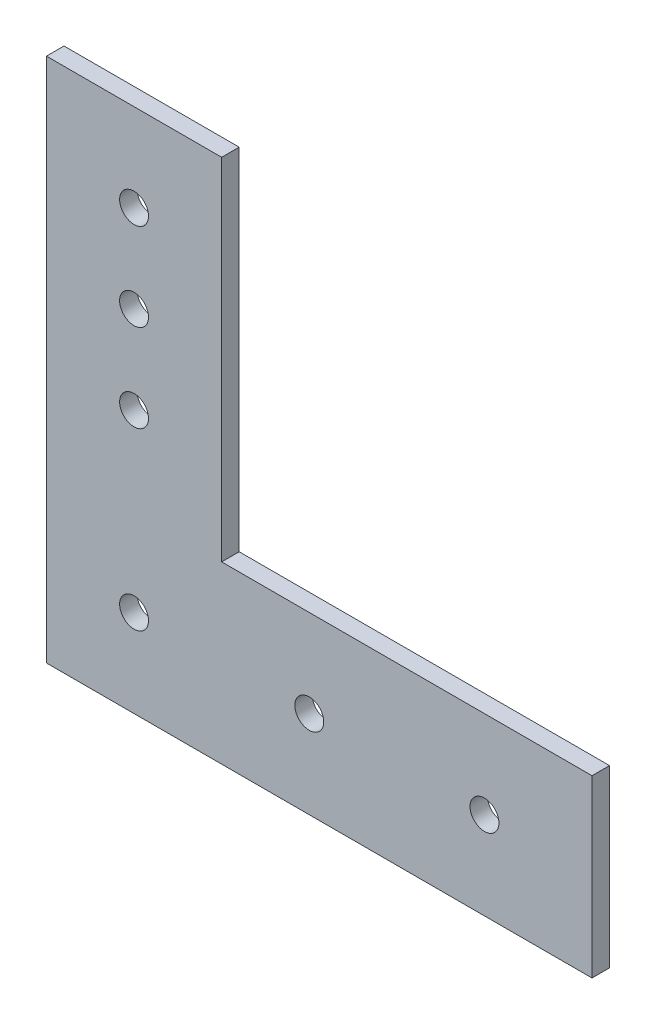
SolidWorks part; units mm, degrees
ref_plane "前视基准面" through (0, 0, 0) normal (0, 0, 1) x (1, 0, 0)
ref_plane "上视基准面" through (0, 0, 0) normal (0, 1, 0) x (1, 0, 0)
ref_plane "右视基准面" through (0, 0, 0) normal (1, 0, 0) x (0, 0, -1)
other "Configuration Table"
sketch "草图1" plane through (0, 0, 0) normal (0, 0, 1) x (1, 0, 0)
  line L0 (10, 10) -> (52.2764, 10)
  line L1 (-10, -10) -> (52.2764, -10)
  line L4 (52.2764, -10) -> (52.2764, 10)
  line L5 (-1.5653, -0.5218) -> (1.5653, 0.5218) construction
  line L6 (-1.5653, 0.5218) -> (1.5653, -0.5218) construction
  line L8 (-10, 10) -> (-10, 50)
  line L9 (-10, 50) -> (10, 50)
  line L10 (10, 10) -> (10, 50)
  line L11 (-10, 10) -> (-10, -10)
  circle A2 centre (20, 0) radius 1.65
  circle A3 centre (0, 20) radius 1.65
  circle A5 centre (0, 40) radius 1.65
  circle A6 centre (0, 30) radius 1.65
  circle A9 centre (0, 0) radius 1.65
  circle A10 centre (40, 0) radius 1.65
  point P0 (0, 0)
  dimension "D11" = 10
  dimension "D9" = 3.3
  dimension "D12" = 10
  dimension "D3" = 3.3
  dimension "D4" = 3.3
  dimension "D2" = 20
  dimension "D5" = 20
  dimension "D6" = 20
  dimension "D7" = 20
  dimension "D8" = 20
  dimension "D10" = 40
extrude "凸台-拉伸1" add sketch "草图1" along normal blind 2
